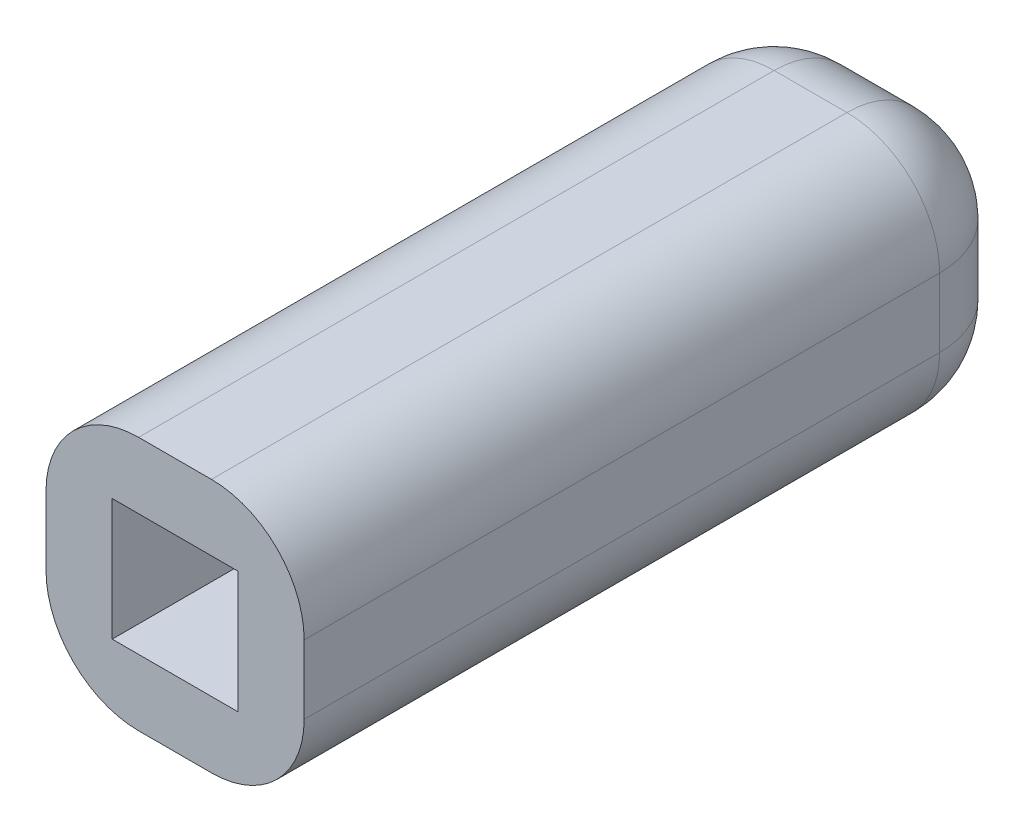
SolidWorks part; units mm, degrees
ref_plane "Front Plane" through (0, 0, 0) normal (0, 0, 1) x (1, 0, 0)
ref_plane "Top Plane" through (0, 0, 0) normal (0, 1, 0) x (1, 0, 0)
ref_plane "Right Plane" through (0, 0, 0) normal (1, 0, 0) x (0, 0, -1)
sketch "Sketch1" plane through (0, 0, 0) normal (0, 0, 1) x (1, 0, 0)
  line L0 (-5, 14.2) -> (14.5, 14.2)
  line L1 (0, 0) -> (9.5, 0)
  line L2 (0, 0) -> (0, 9.2)
  line L3 (0, 9.2) -> (9.5, 9.2)
  line L4 (9.5, 0) -> (9.5, 9.2)
  line L5 (14.5, -5) -> (14.5, 14.2)
  line L6 (-5, -5) -> (14.5, -5)
  line L7 (-5, -5) -> (-5, 14.2)
  dimension "D1" = 9.2
  dimension "D2" = 9.5
  dimension "D3" = 5
extrude "Boss-Extrude1" add sketch "Sketch1" along normal blind 55
extrude "Boss-Extrude2" add sketch "Sketch1<2>" along normal offset from surface (25 mm away) 30 contours L1 L4 L3 L2 region at (4.75, 4.6, 0) up to face at (4.75, 4.6, 55)
sketch "Sketch1<2>" plane through (0, 0, 0) normal (0, 0, 1) x (1, 0, 0) same geometry as "Sketch1"
fillet "Fillet2" radius 7 8 edges at (-5, 4.6, 0) (4.75, -5, 0) (14.5, 4.6, 0) (4.75, 14.2, 0) (14.5, 14.2, 27.5) (-5, 14.2, 27.5) (-5, -5, 27.5) (14.5, -5, 27.5)
